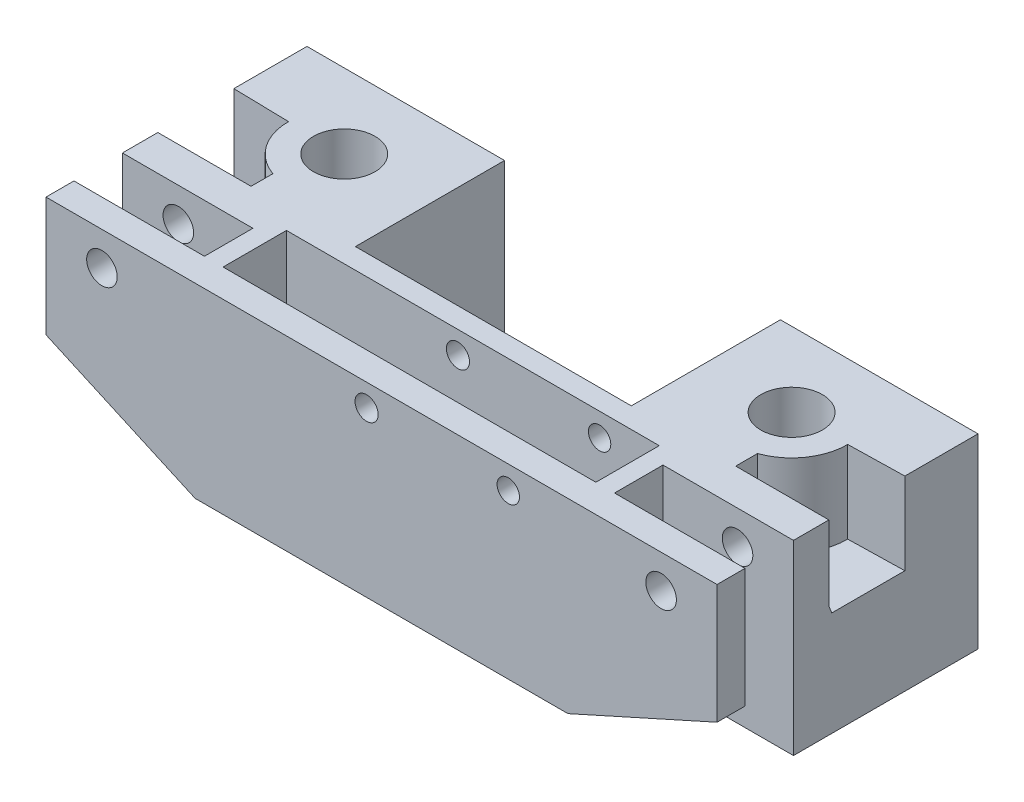
SolidWorks part; units mm, degrees
ref_plane "Front Plane" through (0, 0, 0) normal (0, 0, 1) x (1, 0, 0)
ref_plane "Top Plane" through (0, 0, 0) normal (0, 1, 0) x (1, 0, 0)
ref_plane "Right Plane" through (0, 0, 0) normal (1, 0, 0) x (0, 0, -1)
sketch "Sketch1" plane through (0, 0, 0) normal (0, 1, 0) x (1, 0, 0)
  line L0 (-25, 0) -> (25, 0) construction
  line L1 (25, -25) -> (45, -25)
  line L2 (-25, 25) -> (25, 25) construction
  line L3 (-25, 25) -> (-25, -25)
  line L4 (-25, -25) -> (25, -25) construction
  line L5 (45, -15) -> (25, -15)
  line L6 (-45, -15) -> (-25, -15)
  line L8 (25, -25) -> (25, 25)
  line L9 (0, 10) -> (0, 0) construction
  line L10 (-19.75, -3.35) -> (-25, -3.35) construction
  line L11 (-19.75, -3.35) -> (-19.75, 3.35) construction
  line L12 (-19.75, 3.35) -> (-25, 3.35) construction
  line L13 (-25, -3.35) -> (-25, 3.35) construction
  line L14 (-19.75, -3.35) -> (-25, 3.35) construction
  line L15 (-19.75, 3.35) -> (-25, -3.35) construction
  line L16 (0, 0) -> (0, -10) construction
  line L17 (-22.25, 3.35) -> (-22.25, -3.35) construction
  line L18 (25, -3.35) -> (25, 3.35) construction
  line L19 (19.75, 3.35) -> (25, -3.35) construction
  line L20 (19.75, -3.35) -> (25, 3.35) construction
  line L21 (19.75, -3.35) -> (25, -3.35) construction
  line L22 (22.25, 3.35) -> (22.25, -3.35) construction
  line L23 (19.75, -3.35) -> (19.75, 3.35) construction
  line L24 (19.75, 3.35) -> (25, 3.35) construction
  line L25 (-45, -32.3909) -> (-45, -25)
  line L26 (-25, 25) -> (-45, 25)
  line L28 (-25, -25) -> (-45, -25)
  line L29 (-45, 25) -> (-45, -25)
  line L30 (25, 25) -> (45, 25)
  line L31 (45, 25) -> (45, -25)
  line L33 (4.95, 0.2242) -> (-45, 0.2242) construction
  line L34 (-45, 0.2242) -> (-45, 25) construction
  line L35 (45, 0.2242) -> (45, 25) construction
  line L36 (-4.95, 0.2242) -> (45, 0.2242) construction
  line L44 (-45, 10) -> (45, 10)
  line L45 (-45, -10) -> (45, -10)
  circle A4 centre (0, 0) radius 2.51
  circle A5 centre (10, 0) radius 2.51
  circle A6 centre (-10, 0) radius 2.51
  circle A7 centre (0, 10) radius 2.51
  circle A8 centre (0, -10) radius 2.51
  point P16 (-22.375, 0)
  dimension "D2" = 10
  dimension "D7" = 5.02
  dimension "D13" = 50
  dimension "D15" = 5
  dimension "D3" = 20
  dimension "D5" = 5.25
  dimension "D6" = 6.7
  dimension "D8" = 20
  dimension "D9" = 20
  dimension "D10" = 20
  dimension "D11" = 10
  dimension "D12" = 2.5
  dimension "D14" = 20
extrude "Boss-Extrude1" add sketch "Sketch1" along normal blind 5 contours L2 L3 L4 A8 A7 A6 A5 A4 | L33 L34 | L8 L45 L31 L44 | L29 L45 L3 L44 region at (13.755, 0, 9.4615) region at (35, 0, 0) region at (-35, 0, 0)
sketch "Sketch2" plane through (0, 5, 0) normal (0, 1, 0) x (1, 0, 0)
  line L2 (0, 8.46) -> (0, 10) construction
  line L3 (0, -10) -> (0, -23.44) construction
  circle A0 centre (-30, 0) radius 4.125
  circle A1 centre (30, 0) radius 4.125
  circle A2 centre (-30, 0) radius 6.125
  circle A3 centre (30, 0) radius 6.125
  dimension "D2" = 8.25
  dimension "D3" = 8.25
  dimension "D4" = 2
  dimension "D5" = 2
  dimension "D6" = 30
  dimension "D7" = 30
extrude "Boss-Extrude2" add sketch "Sketch2" along normal blind 20 contours A2 A0 | A3 A1 | A3 | A2 region at (-35.9518, 5, 0) region at (24.0482, 5, 0)
extrude "Boss-Extrude3" add sketch "Sketch1<3>" along normal blind 25 contours L45 L8 L1 L31 | L45 L29 L28 L3 | L31 L5 L8 L1 | L6 L29 L28 L3 region at (35, 0, 20) region at (35, 0, 12.5) region at (-35, 0, 12.5) region at (-35, 0, 20)
sketch "Sketch1<3>" plane through (0, 0, 0) normal (0, 1, 0) x (1, 0, 0) same geometry as "Sketch1"
sketch "Sketch3" plane through (0, 25, 0) normal (0, 1, 0) x (1, 0, 0)
  line L0 (-25, -10) -> (-45, -10) construction
  line L1 (-45, -10) -> (-45, -25) construction
  line L2 (-45, -25) -> (-25, -25) construction
  line L3 (-25, -25) -> (-25, -10) construction
  line L4 (45, -10) -> (25, -10) construction
  line L5 (25, -10) -> (25, -25) construction
  line L6 (25, -25) -> (45, -25) construction
  line L7 (45, -25) -> (45, -10) construction
  line L8 (-25, -10) -> (-45, -10)
  line L9 (-45, -10) -> (-45, -25)
  line L10 (-45, -25) -> (-25, -25)
  line L11 (-25, -25) -> (-25, -10)
  line L12 (45, -10) -> (25, -10)
  line L13 (25, -10) -> (25, -25)
  line L14 (25, -25) -> (45, -25)
  line L15 (45, -25) -> (45, -10)
  line L16 (45, -21.25) -> (27.5, -21.25)
  line L17 (27.5, -21.25) -> (27.5, -14.75)
  line L18 (27.5, -14.75) -> (45, -14.75)
  line L19 (0, 0) -> (0, 25) construction
  line L20 (-27.5, -14.75) -> (-45, -14.75)
  line L21 (-27.5, -21.25) -> (-27.5, -14.75)
  line L22 (-45, -21.25) -> (-27.5, -21.25)
  dimension "D1" = 6.5
  dimension "D2" = 3.75
  dimension "D3" = 2.5
extrude "Cut-Extrude2" cut sketch "Sketch3" against normal offset from surface (21.5 mm away) 3.5 contours L18 L17 L16 L15 | L9 L22 L21 L20 region at (-36.25, 25, 18) region at (36.25, 25, 18) up to face at (0, 0, 8.3333)
sketch "Sketch4" plane through (0, 0, 25) normal (0, 0, 1) x (1, 0, 0)
  line L0 (32.5, 3.5) -> (35, 25) construction
  line L1 (27.5, 14.25) -> (45, 14.25) construction
  line L2 (36.25, 14.25) -> (36.25, 3.5) construction
  line L3 (0, 0) -> (0, 14.499) construction
  line L4 (25, 0) -> (45, 0)
  line L5 (45, 0) -> (45, 25)
  line L6 (45, 25) -> (25, 25)
  line L7 (25, 25) -> (25, 0)
  line L8 (25, 0) -> (45, 0)
  line L9 (45, 0) -> (45, 25)
  line L10 (45, 25) -> (25, 25)
  line L11 (25, 25) -> (25, 0)
  line L12 (45, 3.5) -> (45, 25)
  line L13 (45, 25) -> (27.5, 25)
  line L14 (27.5, 25) -> (27.5, 3.5)
  line L15 (27.5, 3.5) -> (45, 3.5)
  line L16 (45, 3.5) -> (45, 25)
  line L17 (45, 25) -> (27.5, 25)
  line L18 (27.5, 25) -> (27.5, 3.5)
  line L19 (27.5, 3.5) -> (45, 3.5)
  line L20 (-27.5, 25) -> (-27.5, 3.5)
  line L21 (-27.5, 3.5) -> (-45, 3.5)
  circle A0 centre (37.5, 20.5) radius 2.05
  circle A1 centre (-37.5, 20.5) radius 2.05
  dimension "D3" = 4.1
  dimension "D4" = 17
  dimension "D5" = 10
  dimension "D1" = 0
  dimension "D2" = 0
extrude "Cut-Extrude3" cut sketch "Sketch4" against normal up to surface (15 mm away) contours A0 | A1 region at (37.5, 20.5, 25) region at (-37.5, 20.5, 25) up to face at (35, 15, 10)
sketch "Sketch5" plane through (45, 0, 0) normal (1, 0, 0) x (0, 0, -1)
  line L1 (-25, 0) -> (-11.75, 0)
  line L2 (-25, 0) -> (-25, 9)
  line L3 (-25, 9) -> (-11.75, 9)
  line L4 (-11.75, 0) -> (-11.75, 9)
  dimension "D1" = 9
extrude "Cut-Extrude4" cut sketch "Sketch5" against normal through all
sketch "Sketch6" plane through (45, 0, 0) normal (1, 0, 0) x (0, 0, -1)
  line L0 (-10, 15) -> (-6.125, 5)
  line L1 (-10, 25) -> (-10, 5) construction
  line L2 (10, 5) -> (-10, 5) construction
  line L3 (-6.125, 25) -> (-6.125, 5) construction
  line L4 (-6.125, 5) -> (-10, 5)
  line L5 (-10, 5) -> (-10, 15)
extrude "Boss-Extrude4" add sketch "Sketch6" against normal through all
sketch "Sketch9" plane through (0, 5, 0) normal (0, 1, 0) x (1, 0, 0)
  circle A0 centre (30, 0) radius 1.5
  circle A1 centre (-30, 0) radius 1.5
  dimension "D1" = 3
extrude "Cut-Extrude6" cut sketch "Sketch9" against normal through all
sketch "Sketch11" plane through (0, 5, 0) normal (0, 1, 0) x (1, 0, 0)
  line L0 (30, -6.125) -> (45, -6.125) construction
  line L4 (-45, 10) -> (-45, -6.125) construction
  line L5 (-45, -6.125) -> (-30, -6.125) construction
  line L6 (-30, -6.125) -> (30, -6.125) construction
  line L7 (-45, 10) -> (-2.51, 10) construction
  line L8 (2.51, 10) -> (45, 10) construction
  line L9 (45, 10) -> (45, -6.125) construction
  line L10 (-45, 10) -> (-45, -6.125)
  line L11 (-45, 10) -> (-2.51, 10)
  line L12 (2.51, 10) -> (45, 10)
  line L13 (45, 10) -> (45, -6.125)
  line L14 (30, -6.125) -> (45, -6.125)
  line L15 (-30, -6.125) -> (30, -6.125)
  line L16 (-45, -6.125) -> (-30, -6.125)
  line L17 (18.5, -6.125) -> (18.5, 10)
  line L18 (-18.5, -6.125) -> (-18.5, 10)
  line L19 (18.5, -6.125) -> (18.5, -10)
  line L20 (-18.5, -6.125) -> (-18.5, -10)
  line L29 (45, -10) -> (45, -6.125)
  line L30 (45, -6.125) -> (30, -6.125)
  line L31 (30, -6.125) -> (-30, -6.125)
  line L32 (-30, -6.125) -> (-45, -6.125)
  line L33 (-45, -6.125) -> (-45, -10)
  line L34 (-45, -10) -> (-25, -10)
  line L36 (-25, -10) -> (25, -10)
  line L37 (25, -10) -> (45, -10)
  line L39 (45, -10) -> (45, -6.125)
  line L40 (45, -6.125) -> (30, -6.125)
  line L41 (30, -6.125) -> (-30, -6.125)
  line L42 (-30, -6.125) -> (-45, -6.125)
  line L43 (-45, -6.125) -> (-45, -10)
  line L44 (-45, -10) -> (-25, -10)
  line L46 (-25, -10) -> (25, -10)
  line L47 (25, -10) -> (45, -10)
  circle A3 centre (30, 0) radius 6.125 construction
  circle A4 centre (-30, 0) radius 6.125 construction
  circle A5 centre (30, 0) radius 6.125
  circle A6 centre (-30, 0) radius 6.125
  circle A8 centre (10, 0) radius 2.51 construction
  circle A9 centre (-10, 0) radius 2.51 construction
  line M3 (30, -6.125) -> (45, -6.125)
  line M4 (45, -6.125) -> (45, 10)
  line M5 (45, 10) -> (2.51, 10)
  line M8 (-45, 10) -> (-45, -6.125)
  line M9 (-45, -6.125) -> (-30, -6.125)
  circle M10 centre (-30, 0) radius 6.125
  line M11 (-30, -6.125) -> (30, -6.125)
  circle M12 centre (30, 0) radius 6.125
  dimension "D3" = 8.5
  dimension "D1" = 8.5
  dimension "D2" = 0
extrude "Boss-Extrude9" add sketch "Sketch11" along normal blind 9 contours L17 L15 M12 M3 M4 M5 | L47 L39 L15 L19 L46 M3 | L18 L11 M11 M8 M9 M10 | L46 L20 L43 L44 M11 M9 region at (-31.75, 5, -9.6898) region at (-31.75, 5, 8.0625) region at (18.8102, 5, -1.9375) region at (31.75, 5, 8.0625)
sketch "Sketch12" plane through (0, 14, 0) normal (0, 1, 0) x (1, 0, 0)
  line L0 (-45, -10) -> (-25, -10) construction
  line L1 (32.5, -7.0711) -> (27.5, -7.0711) construction
  line L2 (32.5, -7.0711) -> (32.5, -10)
  line L3 (25, -10) -> (18.5, -10)
  line L4 (27.5, -7.0711) -> (27.5, -10)
  line L5 (25, -10) -> (45, -10) construction
  line L6 (-45, -10) -> (-25, -10)
  line L7 (25, -10) -> (45, -10)
  line L8 (30, -7.0711) -> (30, 0) construction
  line L9 (0, 0) -> (0, 26.4876) construction
  line L10 (-30, -7.0711) -> (-30, 0) construction
  line L11 (-32.5, -7.0711) -> (-27.5, -7.0711) construction
  line L12 (-32.5, -7.0711) -> (-32.5, -10)
  line L13 (-27.5, -7.0711) -> (-27.5, -10)
  line L14 (36.125, 0) -> (45, 0.1938)
  line L15 (45, -9.6125) -> (45, 10) construction
  line L16 (45, 0.1938) -> (45, 10)
  line L17 (45, 10) -> (18.5, 10)
  line L18 (18.5, 10) -> (18.5, -9.6125)
  line L19 (18.5, -9.6125) -> (18.5, 10) construction
  line L20 (18.5, -10) -> (18.5, -9.6125)
  line L21 (-25, -10) -> (-18.5, -10)
  line L22 (-18.5, 10) -> (-18.5, -9.6125)
  line L23 (-45, 10) -> (-18.5, 10)
  line L24 (-36.125, 0) -> (-45, 0.1938)
  line L25 (-45, 0.1938) -> (-45, 10)
  line L26 (-18.5, -10) -> (-18.5, -9.6125)
  circle A0 centre (30, 0) radius 7.5
  circle A1 centre (-30, 0) radius 6.125 construction
  circle A2 centre (30, 0) radius 6.125 construction
  circle A3 centre (-30, 0) radius 6.125
  circle A4 centre (30, 0) radius 6.125
  circle A5 centre (-30, 0) radius 7.5
  circle M8 centre (30, 0) radius 6.125
  line M9 (18.5, 10) -> (18.5, -9.6125)
  line M10 (18.5, -9.6125) -> (45, -9.6125)
  line M11 (45, -9.6125) -> (45, 10)
  line M12 (45, 10) -> (18.5, 10)
  dimension "D1" = 15
  dimension "D2" = 15
  dimension "D3" = 5
extrude "Boss-Extrude10" add sketch "Sketch12" along normal up to surface (11 mm away) contours A0 L4 L2 M10 | A0 M8 | A5 L12 L6 L13 | A5 A3 | L4 L7 L2 M10 | A0 L14 L4 M11 M12 M9 M10 | A5 L13 L6 L21 L26 L22 L23 L25 L24 | L20 L3 L7 L4 M10 region at (30, 14, 8.482) region at (30, 14, 7.2879) region at (30, 14, 9.8062) region at (27.1703, 14, 8.3418) region at (23, 14, 9.8062) region at (-30, 14, 8.6763) region at (-27.168, 14, 8.5355) region at (-35.9589, 14, 4.1957) up to face at (30, 25, 4.125)
sketch "Sketch13" plane through (0, 25, 0) normal (0, 1, 0) x (1, 0, 0)
  line L0 (-25, -25) -> (-45, -25) construction
  line L1 (25, -10) -> (-25, -10)
  line L2 (25, -10) -> (25, -25)
  line L3 (25, -25) -> (-25, -25)
  line L4 (-25, -10) -> (-25, -25)
  line L5 (-25, -10) -> (-25, -25) construction
  line L6 (-25, -10) -> (-18.5, -10) construction
  line L8 (25, -25) -> (-25, -25)
  line L9 (25, -25) -> (25, -21.25)
  line L10 (25, -21.25) -> (-25, -21.25)
  line L11 (-25, -25) -> (-25, -21.25)
  line L12 (25, -10) -> (-25, -10)
  line L13 (25, -10) -> (25, -12.75)
  line L14 (25, -12.75) -> (-25, -12.75)
  line L15 (-25, -10) -> (-25, -12.75)
  line M19 (18.5, -10) -> (25, -10)
  line M20 (25, -10) -> (25, -25)
  dimension "D1" = 11.25
  dimension "D2" = 8.5
extrude "Boss-Extrude11" add sketch "Sketch13" against normal up to surface (25 mm away) contours L2 L10 L4 L3 | L14 L1 L4 M20 M19 region at (0, 25, 11.375) region at (0, 25, 23.125) up to face at (-30, 0, 1.5)
sketch "Sketch14" plane through (0, 9, 0) normal (0, -1, 0) x (1, 0, 0)
  line L0 (27.5, 14.75) -> (25, 14.75)
  line L1 (-27.5, 14.75) -> (-25, 14.75)
  line L10 (25, 25) -> (25, 21.25)
  line L11 (25, 21.25) -> (25, 12.75)
  line L12 (25, 12.75) -> (25, 11.75)
  line L13 (25, 11.75) -> (45, 11.75)
  line L14 (45, 11.75) -> (45, 14.75)
  line L15 (45, 14.75) -> (27.5, 14.75)
  line L16 (27.5, 14.75) -> (27.5, 21.25)
  line L17 (27.5, 21.25) -> (45, 21.25)
  line L18 (45, 21.25) -> (45, 25)
  line L19 (45, 25) -> (25, 25)
  line L20 (25, 25) -> (25, 21.25)
  line L21 (25, 21.25) -> (25, 12.75)
  line L22 (25, 12.75) -> (25, 11.75)
  line L23 (25, 11.75) -> (45, 11.75)
  line L24 (45, 11.75) -> (45, 14.75)
  line L25 (45, 14.75) -> (27.5, 14.75)
  line L26 (27.5, 14.75) -> (27.5, 21.25)
  line L27 (27.5, 21.25) -> (45, 21.25)
  line L28 (45, 21.25) -> (45, 25)
  line L29 (45, 25) -> (25, 25)
  line L30 (-25, 11.75) -> (-25, 12.75)
  line L31 (-25, 12.75) -> (-25, 21.25)
  line L32 (-25, 21.25) -> (-25, 25)
  line L33 (-25, 25) -> (-45, 25)
  line L34 (-45, 25) -> (-45, 21.25)
  line L35 (-45, 21.25) -> (-27.5, 21.25)
  line L36 (-27.5, 21.25) -> (-27.5, 14.75)
  line L37 (-27.5, 14.75) -> (-45, 14.75)
  line L38 (-45, 14.75) -> (-45, 11.75)
  line L39 (-45, 11.75) -> (-25, 11.75)
  line L40 (-25, 11.75) -> (-25, 12.75)
  line L41 (-25, 12.75) -> (-25, 21.25)
  line L42 (-25, 21.25) -> (-25, 25)
  line L43 (-25, 25) -> (-45, 25)
  line L44 (-45, 25) -> (-45, 21.25)
  line L45 (-45, 21.25) -> (-27.5, 21.25)
  line L46 (-27.5, 21.25) -> (-27.5, 14.75)
  line L47 (-27.5, 14.75) -> (-45, 14.75)
  line L48 (-45, 14.75) -> (-45, 11.75)
  line L49 (-45, 11.75) -> (-25, 11.75)
  line M22 (25, 21.25) -> (25, 12.75)
  line M23 (25, 12.75) -> (25, 11.75)
  line M24 (25, 11.75) -> (45, 11.75)
  line M25 (45, 11.75) -> (45, 14.75)
  line M26 (45, 14.75) -> (27.5, 14.75)
  dimension "D1" = 0
  dimension "D2" = 0
extrude "Boss-Extrude12" add sketch "Sketch14" along normal up to surface (9 mm away) contours L48 L49 L40 L41 L1 L47 | L0 M26 M22 M23 M24 M25 region at (35, 9, 13.25) region at (-35, 9, 13.25) up to face at (0, 0, 8.745)
sketch "Sketch15" plane through (0, 0, 25) normal (0, 0, 1) x (1, 0, 0)
  line L0 (-45, 9) -> (-25, 0)
  line L1 (25, 0) -> (45, 9)
  line L11 (45, 25) -> (-45, 25)
  line L12 (-45, 25) -> (-45, 9)
  line L13 (-45, 9) -> (-25, 9)
  line L14 (-25, 9) -> (-25, 0)
  line L15 (-25, 0) -> (25, 0)
  line L16 (25, 0) -> (25, 9)
  line L17 (25, 9) -> (45, 9)
  line L18 (45, 9) -> (45, 25)
  line L19 (45, 25) -> (-45, 25)
  line L20 (-45, 25) -> (-45, 9)
  line L21 (-45, 9) -> (-25, 9)
  line L22 (-25, 9) -> (-25, 0)
  line L23 (-25, 0) -> (25, 0)
  line L24 (25, 0) -> (25, 9)
  line L25 (25, 9) -> (45, 9)
  line L26 (45, 9) -> (45, 25)
  point P9 (45, 9)
  line M12 (-45, 9) -> (-25, 9)
  line M13 (-25, 9) -> (-25, 0)
  line M15 (25, 0) -> (25, 9)
  line M16 (25, 9) -> (45, 9)
  dimension "D1" = 0
extrude "Boss-Extrude13" add sketch "Sketch15" against normal up to surface (3.75 mm away) contours L0 M12 M13 | L1 M15 M16 region at (-31.6667, 6, 25) region at (31.6667, 6, 25) up to face at (36.25, 17, 21.25)
sketch "Sketch16" plane through (0, 0, 25) normal (0, 0, 1) x (1, 0, 0)
  line L4 (-25, 25) -> (-25, 0)
  line L5 (-25, 0) -> (25, 0)
  line L6 (25, 0) -> (45, 9)
  line L7 (45, 9) -> (45, 25)
  line L8 (45, 25) -> (-45, 25)
  line L9 (-45, 25) -> (-45, 9)
  line L10 (-45, 9) -> (-25, 0)
  line L11 (-25, 0) -> (25, 0)
  line L12 (25, 0) -> (45, 9)
  line L13 (45, 9) -> (45, 25)
  line L14 (45, 25) -> (-45, 25)
  line L15 (-45, 25) -> (-45, 9)
  line L16 (-45, 9) -> (-25, 0)
  line L17 (-25, 0) -> (25, 0)
  line L18 (25, 0) -> (25, 25)
  line L19 (25, 25) -> (-25, 25)
  line L20 (-25, 25) -> (-25, 0)
  line L21 (-25, 0) -> (25, 0)
  line L22 (25, 0) -> (25, 25)
  line L23 (25, 25) -> (-25, 25)
  circle A0 centre (17, 21.9) radius 1.5
  circle A1 centre (-1.9997, 22) radius 1.55
  point P12 (17, 19.5271)
  dimension "D3" = 3.1
  dimension "D4" = 3
  dimension "D6" = 19
  dimension "D5" = 8
  dimension "D7" = 3.1
  dimension "D8" = 3
  dimension "D1" = 0
  dimension "D2" = 0
extrude "Cut-Extrude7" cut sketch "Sketch16" against normal blind 38 contours A1 | A0 region at (17, 21.9, 25) region at (-1.9997, 22, 25)
